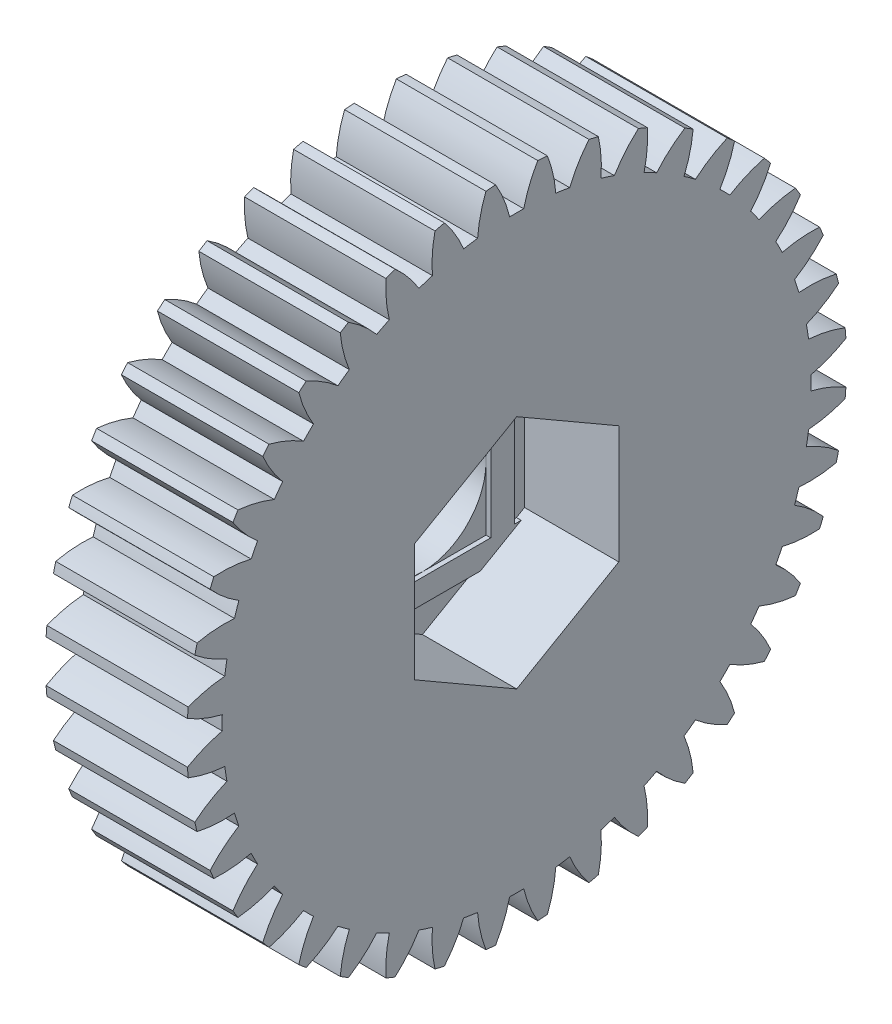
SolidWorks part; units mm, degrees
ref_plane "Plane1" through (0, 0, 0) normal (0, 0, 1) x (1, 0, 0)
ref_plane "Plane2" through (0, 0, 0) normal (0, 1, 0) x (1, 0, 0)
ref_plane "Plane3" through (0, 0, 0) normal (1, 0, 0) x (0, 0, -1)
sketch "HoldingSke" plane through (0, 0, 0) normal (0, 1, 0) x (1, 0, 0)
  line L0 (0, 0) -> (0.766, -0.6428)
  line L1 (-15, 0) -> (100, 0) construction
  line L2 (0, 0) -> (-2.1039, 2.3779)
  line L3 (0, 0) -> (-11.863, 4.5341)
  line L4 (0, 0) -> (6.6156, 5.5511)
  line L5 (0, 0) -> (-46.8476, -17.4728)
  line L6 (0, 0) -> (-7.4607, -5.0337)
  line L7 (-2.1039, 2.3779) -> (8.6586, 51.2059)
  line L8 (-76.2, 54.61) -> (-75.5, 54.61)
  line L9 (-71.009, 38.7566) -> (-53.1078, 45.2721)
  line L10 (-76.2, 71.12) -> (104.1128, 71.12)
  line L11 (0, 0) -> (-9, 0)
  line L12 (-76.2, 101.6) -> (-76.162, 101.6)
  line L13 (24.9733, 27.94) -> (52.9518, 28.4284)
  line L14 (24.9733, 27.94) -> (24.9743, 27.94)
  line L15 (24.9733, 27.94) -> (100.4006, 29.5858)
  line L16 (-63.627, -1) -> (-12.827, -1)
  circle A0 centre (0, 0) radius 2
  circle A1 centre (0, 0) radius 18.749
  circle A2 centre (0, 0) radius 37.5
  circle A3 centre (0, 0) radius 2
  dimension "MHD" = 37.498
  dimension "Hub_dia" = 75
  dimension "Bore" = 4
  dimension "MBD" = 4
  dimension "Num_teeth" = 40
  dimension "Pitch" = 1
  dimension "Overall_len" = 50
  dimension "Show_teeth" = 40
  dimension "Thickness" = 9
  dimension "OAL" = 50.0001
  dimension "T_dim" = 0.7
  dimension "Ap" = 20
  dimension "H" = 19.05
  dimension "Pitch_radius" = 180.3128
  dimension "Width" = 9
  dimension "Backlash" = 0.038
  dimension "Addendum_fac" = 1
  dimension "Dedendum_fac" = 1.25
  dimension "Clearance_fac" = 0.25
  dimension "Dedendum_add" = 0.001
  dimension "Module" = 1
sketch "BasProSke" plane through (0, 0, 0) normal (0, 1, 0) x (1, 0, 0)
  line L0 (-10, 0) -> (60, 0) construction
  line L1 (0, 0) -> (0, 21)
  line L2 (0, 0) -> (9, 0)
  line L3 (9, 0) -> (9, 21)
  line L4 (9, 21) -> (0, 21)
  dimension "Thickness" = 9
  dimension "Diameter" = 42
revolve "Base-Revolve" add sketch "BasProSke" angle 360 about L0
sketch "TooCutSke" plane through (0, 0, 0) normal (1, 0, 0) x (0, 0, -1)
  line L1 (0, 0) -> (0, 107) construction
  line L2 (0, 0) -> (-0.8517, 19.9819) construction
  line L3 (0, 0) -> (-3.1363, 39.8509) construction
  line L4 (-0.8517, 19.9819) -> (-1.5682, 19.9255) construction
  arc A0 (0.4487, 18.7436) -> (-0.4487, 18.7436) centre (0, 0) ccw
  arc A1 (1.3547, 20.9817) -> (-1.3547, 20.9817) centre (0, 0) ccw
  circle A2 centre (0, 0) radius 20 construction
  circle A3 centre (0, 0) radius 18.7939 construction
  arc A4 (-0.4487, 18.7436) -> (-1.3547, 20.9817) centre (-8.2322, 16.895) ccw
  arc A5 (1.3547, 20.9817) -> (0.4487, 18.7436) centre (8.2322, 16.895) ccw
  dimension "Root_dia" = 37.498
  dimension "Overcut_dia" = 42.0508
  dimension "Pitch_dia" = 40
  dimension "Base_dia" = 37.5877
  dimension "Flank_rad" = 8
  dimension "Half_ang" = 4.5
  dimension "Half_CT" = 0.7187
extrude "ToothCut" cut sketch "TooCutSke" along normal through all
fillet "Breaks" [suppressed] radius 0.02 tangent propagation no
fillet "RootFillets" [suppressed] radius 0.251
pattern_circular "TeethCuts" count 40 every 9 about axis through (-10, 0, 0) along (1, 0, 0) of "ToothCut", "RootFillets", "Breaks"
sketch "HubNeaOneSke" plane through (0, 0, 0) normal (-1, 0, 0) x (0, 0, 1)
  circle A0 centre (0, 0) radius 18.749
  dimension "Diameter" = 37.498
extrude "HubNearOne" [suppressed] add sketch "HubNeaOneSke" along normal blind 41.0001
sketch "HubNeaBotSke" plane through (0, 0, 0) normal (-1, 0, 0) x (0, 0, 1)
  circle A0 centre (0, 0) radius 18.749
  dimension "Diameter" = 37.498
extrude "HubNearBoth" [suppressed] add sketch "HubNeaBotSke" along normal blind 20.5
ref_plane "FarPln" through (9, 0, 0) normal (1, 0, 0) x (0, 0, -1)
sketch "HubFarSke" plane through (9, 0, 0) normal (1, 0, 0) x (0, 0, -1)
  circle A0 centre (0, 0) radius 18.749
  dimension "Diameter" = 37.498
extrude "HubFar" [suppressed] add sketch "HubFarSke" along normal blind 20.5
sketch "BorSke" plane through (0, 0, 0) normal (1, 0, 0) x (0, 0, -1)
  circle A0 centre (0, 0) radius 2
  dimension "Diameter" = 4
extrude "Bore" cut sketch "BorSke" along normal mid plane 100.0001
sketch "KeySke" plane through (0, 0, 0) normal (1, 0, 0) x (0, 0, -1)
  line L0 (-0.8, 0) -> (-0.8, 2.7)
  line L1 (-0.8, 2.7) -> (0.8, 2.7)
  line L2 (0.8, 2.7) -> (0.8, 0)
  line L3 (0, 0) -> (0, 34) construction
  line L4 (-0.8, 0) -> (0.8, 0)
  dimension "Offset" = 2.7
  dimension "Width" = 1.6
extrude "Keyway" [suppressed] cut sketch "KeySke" along normal mid plane 100.0001
pattern_circular "Keyway2" [suppressed] count 2 every 90 about axis through (-10, 0, 0) along (1, 0, 0) reverse direction yes
sketch "Sketch1" plane through (9, 0, 0) normal (1, 0, 0) x (0, 0, -1)
  line L1 (0, 7.5056) -> (-6.5, 3.7528)
  line L2 (-6.5, 3.7528) -> (-6.5, -3.7528)
  line L3 (-6.5, -3.7528) -> (0, -7.5056)
  line L4 (0, -7.5056) -> (6.5, -3.7528)
  line L5 (6.5, -3.7528) -> (6.5, 3.7528)
  line L6 (6.5, 3.7528) -> (0, 7.5056)
  circle A0 centre (0, 0) radius 7.5056
  circle A2 centre (0, 0) radius 6.5 construction
  circle A3 centre (0, 0) radius 4.05
  dimension "D1" = 8.1
  dimension "D2" = 13
extrude "Cut-Extrude1" cut sketch "Sketch1" against normal blind 6 contours L1 L2 L3 L4 L5 L6
extrude "Cut-Extrude2" cut sketch "Sketch1<7>" against normal through all contours A3 region at (9, 0, 0)
sketch "Sketch1<7>" plane through (9, 0, 0) normal (1, 0, 0) x (0, 0, -1) same geometry as "Sketch1"
sketch "Sketch2" plane through (0, 0, 0) normal (-1, 0, 0) x (0, 0, 1)
  circle A0 centre (0, 0) radius 6
  circle A1 centre (0, 0) radius 4
  dimension "D1" = 12
  dimension "D2" = 8
extrude "Boss-Extrude1" add sketch "Sketch2" along normal blind 1.8
sketch "Sketch3" plane through (3, 0, 0) normal (1, 0, 0) x (0, 0, -1)
  line L1 (4.05, 4.05) -> (-4.05, 4.05)
  line L2 (4.05, 4.05) -> (4.05, -4.05)
  line L3 (4.05, -4.05) -> (-4.05, -4.05)
  line L4 (-4.05, 4.05) -> (-4.05, -4.05)
  line L6 (5.55, 5.55) -> (5.55, -5.55)
  line L7 (5.55, -5.55) -> (-5.55, -5.55)
  line L8 (-5.55, 5.55) -> (-5.55, -5.55)
  line L9 (5.55, 5.55) -> (-5.55, 5.55)
  line L10 (5.55, 4.05) -> (5.9852, 4.05)
  line L11 (6.5, 3.7528) -> (0, 7.5056) construction
  line L12 (5.55, -4.05) -> (5.9852, -4.05)
  line L13 (0, -7.5056) -> (6.5, -3.7528) construction
  line L14 (-5.55, -4.05) -> (-5.9852, -4.05)
  line L15 (-6.5, -3.7528) -> (0, -7.5056) construction
  line L16 (-5.55, 4.05) -> (-5.9852, 4.05)
  line L17 (0, 7.5056) -> (-6.5, 3.7528) construction
  circle A0 centre (0, 0) radius 4.05 construction
  line M10 (6.5, 3.7528) -> (0, 7.5056)
  line M11 (0, 7.5056) -> (-6.5, 3.7528)
  line M13 (-6.5, -3.7528) -> (0, -7.5056)
  line M14 (0, -7.5056) -> (6.5, -3.7528)
  dimension "D1" = 1.5
extrude "Boss-Extrude2" add sketch "Sketch3" along normal blind 0.3 contours L9 L8 L7 L6 L4 L1 L2 L3 M10 M11 M13 M14 | L12 L6 M14 | L6 L10 M10 | L16 L8 M11 | L8 L14 M13 region at (3, 0, -5.393) region at (3, 4.1338, -5.6951) region at (3, -4.1338, -5.6951) region at (3, 4.1338, 5.6951) region at (3, -4.1338, 5.6951)
equation "' \"Module@HoldingSke\" = 6.35"
equation "' \"Num_teeth@HoldingSke\" = 12"
equation "' \"Ap@HoldingSke\" =  20"
equation "' \"Ap@HoldingSke\" = 20"
equation "' \"Width@HoldingSke\" = 0.5 * 25.4"
equation "' \"Hub_dia@HoldingSke\"= 1 * 25.4"
equation "' \"Hub_dia@HoldingSke\" = 1 * 25.4"
equation "' \"Overall_len@HoldingSke\" = 1.0 * 25.4"
equation "' \"Bore@HoldingSke\" = 0.75 * 25.4"
equation "' \"T_dim@HoldingSke\" = 0.1 * 25.4"
equation "' \"Width@KeySke\" = 0.25 * 25.4"
equation "' \"Show_teeth@HoldingSke\" = 13"
equation "' \"Backlash@HoldingSke\" = 0.009 * 25.4"
equation "' \"Addendum_fac@HoldingSke\" = 1.0"
equation "' \"Dedendum_fac@HoldingSke\" = 1.25"
equation "' \"Dedendum_add@HoldingSke\" = 0.00005 * 25.4"
equation "' \"Clearance_fac@HoldingSke\" = 0.25"
equation "\"Pitch@HoldingSke\" = 1 / \"Module@HoldingSke\""
equation "\"Overcut_dia@TooCutSke\" = (\"Num_teeth@HoldingSke\" + 2 * \"Addendum_fac@HoldingSke\") / \"Pitch@HoldingSke\" + 0.002 * 25.4"
equation "\"Pitch_dia@TooCutSke\" = \"Num_teeth@HoldingSke\" / \"Pitch@HoldingSke\""
equation "\"Base_dia@TooCutSke\" = \"Num_teeth@HoldingSke\" / \"Pitch@HoldingSke\" * cos((\"Ap@HoldingSke\"  * 3.14159265 / 180))"
equation "\"Root_dia@TooCutSke\" = (\"Num_teeth@HoldingSke\" + 2) / \"Pitch@HoldingSke\" - 2 * (\"Addendum_fac@HoldingSke\" + \"Dedendum_fac@HoldingSke\") / \"Pitch@HoldingSke\" - \"Dedendum_add@HoldingSke\" * 2"
equation "\"Half_ang@TooCutSke\" = 180 / \"Num_teeth@HoldingSke\""
equation "\"Half_CT@TooCutSke\" = \"Num_teeth@HoldingSke\" / \"Pitch@HoldingSke\" * sin((3.14159265 / 2 / \"Num_teeth@HoldingSke\")) / 2 - 7 * \"Backlash@HoldingSke\" / 4"
equation "\"Flank_rad@TooCutSke\" = \"Num_teeth@HoldingSke\" / \"Pitch@HoldingSke\" / 5"
equation "\"Radius@RootFillets\" = \"Clearance_fac@HoldingSke\" / \"Pitch@HoldingSke\" + \"Dedendum_add@HoldingSke\""
equation "\"Break_rad@Breaks\" = 0.02 / \"Pitch@HoldingSke\""
equation "\"Thickness@HoldingSke\" = \"Width@HoldingSke\""
equation "\"OAL@HoldingSke\" = \"Thickness@HoldingSke\""
equation "\"MHD@HoldingSke\" = (\"Num_teeth@HoldingSke\" + 2) / \"Pitch@HoldingSke\" - 2 * (\"Addendum_fac@HoldingSke\" + \"Dedendum_fac@HoldingSke\")  / \"Pitch@HoldingSke\" - \"Dedendum_add@HoldingSke\" * 2"
equation "\"MBD@HoldingSke\" = (\"Num_teeth@HoldingSke\" + 2) / \"Pitch@HoldingSke\" - 2 * (\"Addendum_fac@HoldingSke\" + \"Dedendum_fac@HoldingSke\")  / \"Pitch@HoldingSke\" - \"Dedendum_add@HoldingSke\" * 2 - 0.002 * 25.4"
equation "\"MHD@HoldingSke\" = ((sgn( \"MHD@HoldingSke\" - \"Hub_dia@HoldingSke\" )-1)*( \"MHD@HoldingSke\" - \"Hub_dia@HoldingSke\" ))/-2+ \"Hub_dia@HoldingSke\""
equation "\"MBD@HoldingSke\" = ((sgn( \"MBD@HoldingSke\" - \"Bore@HoldingSke\" )-1)*( \"MBD@HoldingSke\" - \"Bore@HoldingSke\" ))/-2+ \"Bore@HoldingSke\""
equation "\"OAL@HoldingSke\" = ((sgn( \"OAL@HoldingSke\" - \"Overall_len@HoldingSke\" )+1)*( \"OAL@HoldingSke\" - \"Overall_len@HoldingSke\" ))/2 + \"Overall_len@HoldingSke\" + 0.000002 * 25.4"
equation "\"Num_teeth@TeethCuts\" = int( \"Show_teeth@HoldingSke\" ) + 1"
equation "\"Num_teeth@TeethCuts\" = ((sgn( \"Num_teeth@TeethCuts\" - \"Num_teeth@HoldingSke\" )-1)*( \"Num_teeth@TeethCuts\" - \"Num_teeth@HoldingSke\" ))/-2+ \"Num_teeth@HoldingSke\""
equation "\"Num_teeth@TeethCuts\" = ((sgn( \"Num_teeth@TeethCuts\" - 2.0)+1)*( \"Num_teeth@TeethCuts\" - 2.0))/2 +2.0"
equation "\"Angle@TeethCuts\" = 360.0 / \"Num_teeth@HoldingSke\""
equation "\"Diameter@BasProSke\" = (\"Num_teeth@HoldingSke\" + 2 * \"Addendum_fac@HoldingSke\") / \"Pitch@HoldingSke\""
equation "\"Thickness@BasProSke\"  = \"Thickness@HoldingSke\""
equation "' \"Fillet_rad@BasProSke\" =  \"Thickness@HoldingSke\" * 0.05"
equation "' \"Fillet_rad@BasProSke\" = \"Thickness@HoldingSke\" * 0.05"
equation "\"MHD@HoldingSke\" = ((sgn( \"MHD@HoldingSke\" - \"Root_dia@TooCutSke\" )-1)*( \"MHD@HoldingSke\" - \"Root_dia@TooCutSke\" ))/-2+ \"Root_dia@TooCutSke\""
equation "\"Diameter@HubNeaOneSke\" = \"MHD@HoldingSke\""
equation "\"Length@HubNearOne\" = \"OAL@HoldingSke\" - \"Thickness@BasProSke\""
equation "\"Diameter@HubNeaBotSke\" = \"MHD@HoldingSke\""
equation "\"Length@HubNearBoth\" = ( \"OAL@HoldingSke\" - \"Thickness@BasProSke\" ) / 2.0"
equation "\"Thickness@FarPln\" = \"Thickness@BasProSke\""
equation "\"Diameter@HubFarSke\" = \"MHD@HoldingSke\""
equation "\"Length@HubFar\" = ( \"OAL@HoldingSke\" - \"Thickness@BasProSke\" ) / 2.0"
equation "\"Diameter@BorSke\" = \"MBD@HoldingSke\""
equation "\"D1@Bore\" = \"OAL@HoldingSke\" * 2.0"
equation "\"D1@Keyway\" = \"OAL@HoldingSke\" * 2.0"
equation "\"Offset@KeySke\" = \"T_dim@HoldingSke\" + \"MBD@HoldingSke\" / 2.0"
